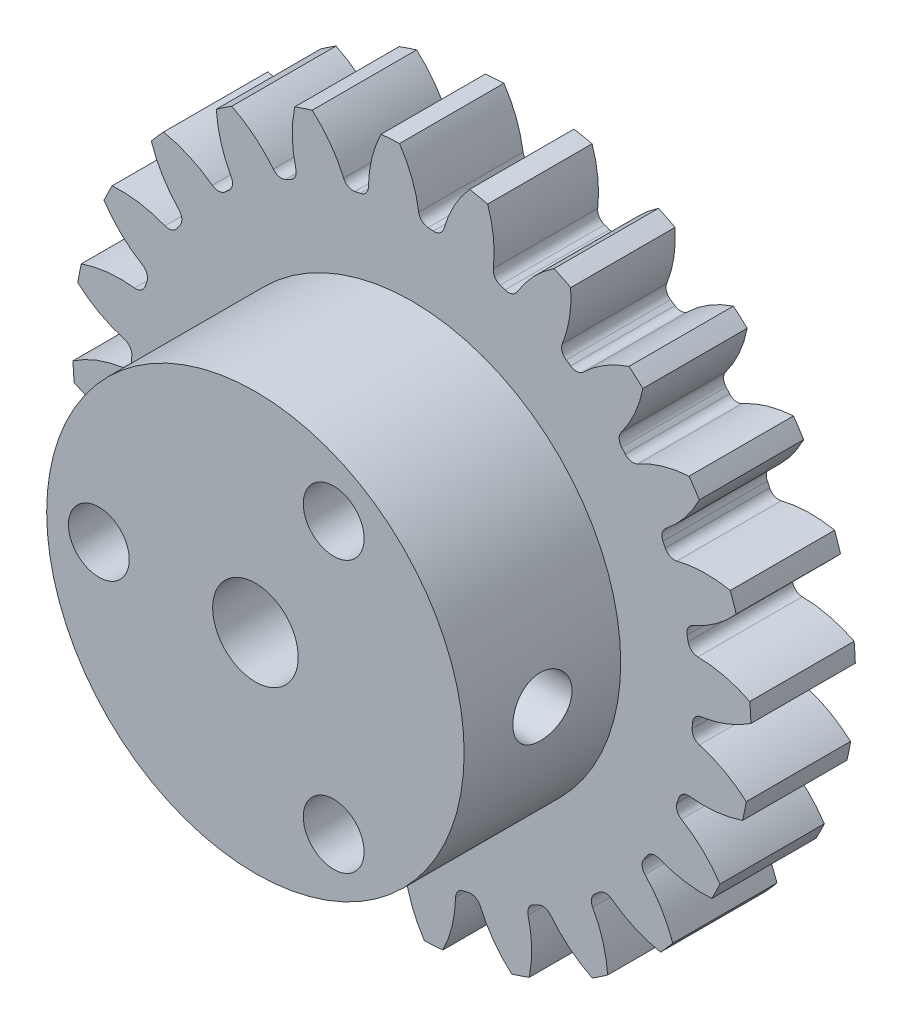
SolidWorks part; units mm, degrees
ref_plane "Front" through (0, 0, 0) normal (0, 0, 1) x (1, 0, 0)
ref_plane "Top" through (0, 0, 0) normal (0, 1, 0) x (1, 0, 0)
ref_plane "Right" through (0, 0, 0) normal (1, 0, 0) x (0, 0, -1)
sketch "Sketch3" plane through (0, 0, 0) normal (0, 0, 1) x (1, 0, 0)
  circle A0 centre (0, 0) radius 20.6375
  dimension "od" = 41.275
extrude "gearBody" add sketch "Sketch3" along normal blind 6.35
sketch "Sketch2" plane through (0, 0, 0) normal (0, 0, 1) x (1, 0, 0)
  line L0 (0, 0) -> (16.5385, 6.8505) construction
  line L1 (22.0347, -5.709) -> (0, 0) construction
  line L2 (0, 0) -> (36.3143, 0) construction
  line L3 (19.05, -0.043) -> (18.8852, -2.5004) construction
  line L5 (18.9676, -1.2717) -> (0, 0) construction
  line L7 (0, 0) -> (17.9011, 0) construction
  arc A0 (17.8975, -0.3593) -> (17.7853, -2.0332) centre (0, 0) ccw construction
  arc A1 (20.6236, 0.7563) -> (20.3381, -3.5027) centre (0, 0) ccw construction
  arc A2 (19.05, -0.043) -> (18.8852, -2.5004) centre (0, 0) ccw construction
  arc A3 (17.0444, -1.304) -> (17.0659, -0.983) centre (0, 0) ccw
  arc A4 (22.0347, -5.709) -> (17.4884, -1.9416) centre (15.476, -8.9969) ccw
  arc A5 (22.0347, -5.709) -> (22.5996, 2.7164) centre (0, 0) ccw
  arc A6 (22.5996, 2.7164) -> (17.5911, -0.4103) centre (16.5385, 6.8505) cw
  arc A7 (17.0659, -0.983) -> (17.5911, -0.4103) centre (17.6793, -1.0183) cw
  arc A8 (17.4884, -1.9416) -> (17.0444, -1.304) centre (17.657, -1.3509) cw
  point P6 (22.5996, 2.7164)
  point P22 (22.0347, -5.709)
  dimension "baseDia" = 35.8023
  dimension "od" = 41.275
  dimension "pd" = 38.1
  dimension "rd" = 34.1884
  dimension "rFillet" = 0.6144
  dimension "pointX" = 22.5996
  dimension "pointY" = 2.7164
  dimension "CTT" = 2.4574
  dimension "flankCenterAngle" = 22.5
extrude "toothCut" cut sketch "Sketch2" along normal through all
pattern_circular "CirPattern1" count 24 over 360 about axis through (0, 0, 6.35) along (0, 0, -1) of "toothCut"
sketch "hub1Dia" plane through (0, 0, 0) normal (0, 0, -1) x (-1, 0, 0)
  circle A0 centre (0, 0) radius 12.7
  dimension "hub1Dia" = 25.4
sketch "hub2Dia" plane through (0, 0, 6.35) normal (0, 0, 1) x (1, 0, 0)
  circle A0 centre (0, 0) radius 12.7
  dimension "hub2dia" = 25.4
sketch "boreDia" plane through (0, 0, 0) normal (0, 0, 1) x (1, 0, 0)
  circle A0 centre (0, 0) radius 6.35
  dimension "boreDia" = 12.7
extrude "Boss-Extrude1" add sketch "hub2Dia" along normal blind 9.525
sketch "Sketch4" plane through (0, 0, 0) normal (0, 0, -1) x (-1, 0, 0)
  circle A0 centre (9.525, 0) radius 1.85
  circle A1 centre (-4.7625, -8.2489) radius 1.85
  circle A2 centre (-4.7625, 8.2489) radius 1.85
  point P9 (0, 0)
  dimension "D2" = 3.7
  dimension "D1" = 9.525
  dimension "D3" = 3
extrude "Cut-Extrude1" cut sketch "Sketch4" against normal through all
sketch "Sketch5" plane through (0, 0, 0) normal (0, 0, -1) x (-1, 0, 0)
  circle A0 centre (0, 0) radius 2.6035
  dimension "D1" = 5.207
extrude "Cut-Extrude2" cut sketch "Sketch5" against normal through all
sketch "Sketch6" plane through (0, 0, 0) normal (1, 0, 0) x (0, 0, -1)
  line L0 (-15.875, 12.7) -> (-15.875, -12.7) construction
  circle A0 centre (-11.1125, 0) radius 1.8
  dimension "D2" = 3.6
  dimension "D1" = 4.7625
extrude "Cut-Extrude3" cut sketch "Sketch6" along normal through all
equation "\"D2@Sketch4\"=3.7mm"
equation "\"D1@Sketch5\"=\"tightTol\" + 0.20"
equation "\"tightTol\" = 0.005in"
equation "\"normTol\"= 0.01in"
equation "\"looseTol\"= 0.02in"
equation "\"D2@Sketch6\"=3.6mm"
